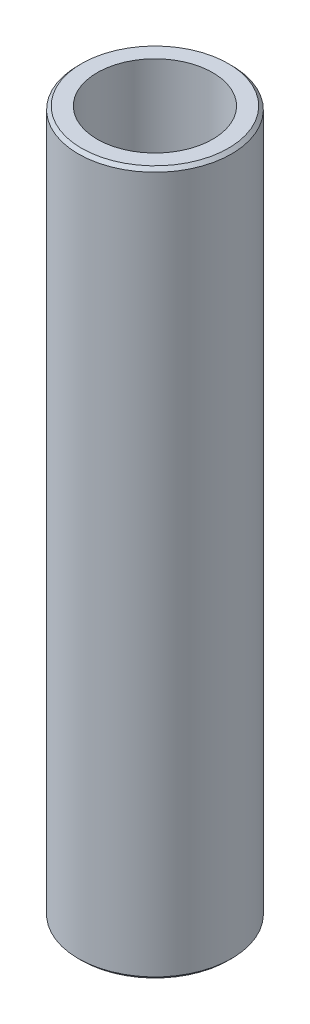
SolidWorks part; units mm, degrees
ref_plane "Front Plane" through (0, 0, 0) normal (0, 0, 1) x (1, 0, 0)
ref_plane "Top Plane" through (0, 0, 0) normal (0, 1, 0) x (1, 0, 0)
ref_plane "Right Plane" through (0, 0, 0) normal (1, 0, 0) x (0, 0, -1)
sketch "Sketch1" plane through (0, 0, 0) normal (0, 1, 0) x (1, 0, 0)
  circle A0 centre (0, 0) radius 37.5
  dimension "SHAFT_OD" = 75
extrude "Boss-Extrude1" add sketch "Sketch1" along normal blind 344.0706
sketch "Sketch2" plane through (0, 0, 0) normal (0, 1, 0) x (1, 0, 0)
  circle A0 centre (0, 0) radius 28.2471
  dimension "BORE_D" = 56.4942
extrude "Cut-Extrude1" cut sketch "Sketch2" along normal through all
chamfer "Chamfer1" distance 1.5962 angle 45 2 edges at (0, 344.0706, 37.5) (0, 0, 37.5)
